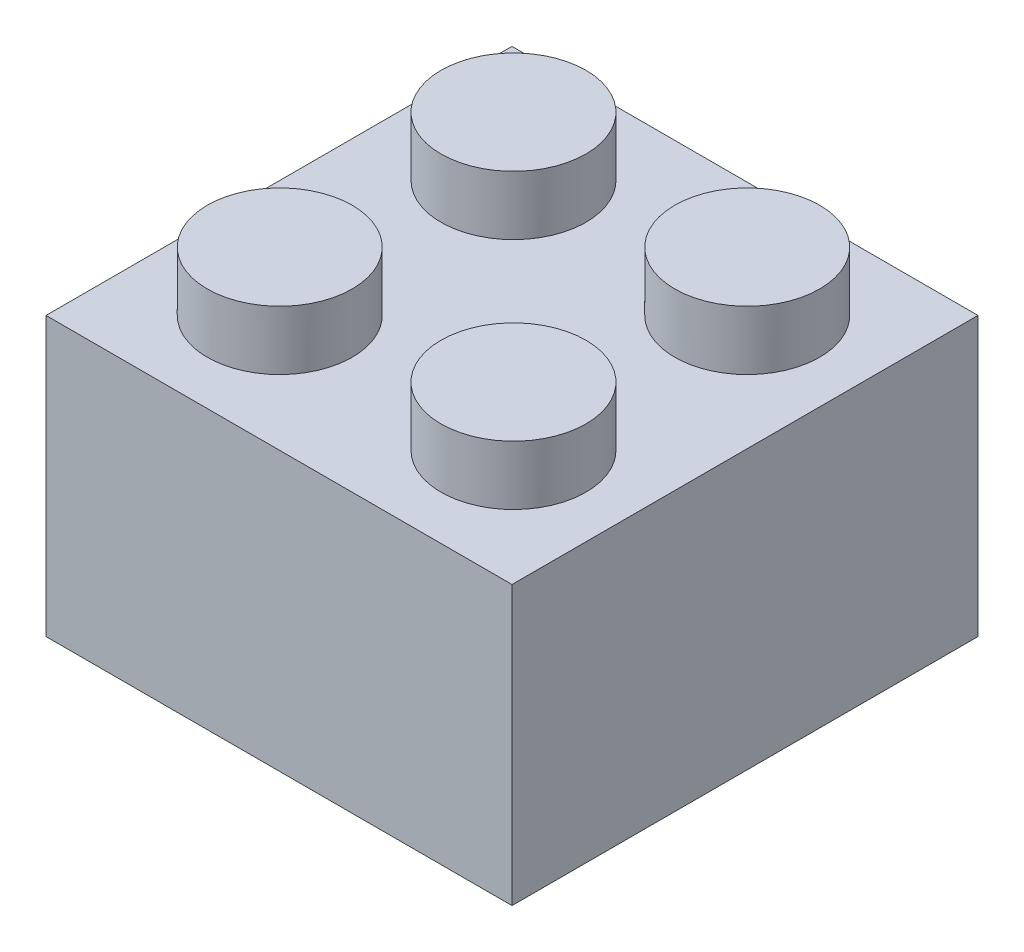
SolidWorks part; units mm, degrees
ref_plane "Front Plane" through (0, 0, 0) normal (0, 0, 1) x (1, 0, 0)
ref_plane "Top Plane" through (0, 0, 0) normal (0, 1, 0) x (1, 0, 0)
ref_plane "Right Plane" through (0, 0, 0) normal (1, 0, 0) x (0, 0, -1)
sketch "stencil" plane through (0, 0, 0) normal (0, 1, 0) x (1, 0, 0)
  line L2 (0, 0) -> (0, 3.95) construction
  line L29 (0, 0) -> (3.95, 0) construction
  line L30 (3.95, 0) -> (3.95, 3.95) construction
  line L31 (7.9, 0) -> (7.9, 3.95) construction
  line L32 (11.85, 0) -> (11.85, 3.95) construction
  line L36 (3.95, 3.95) -> (3.95, 7.9) construction
  line L37 (7.9, 3.95) -> (7.9, 7.9) construction
  line L38 (11.85, 3.95) -> (11.85, 7.9) construction
  line L39 (3.95, 7.9) -> (3.95, 11.85) construction
  line L40 (7.9, 7.9) -> (7.9, 11.85) construction
  line L41 (11.85, 7.9) -> (11.85, 11.85) construction
  line L52 (3.95, 11.85) -> (3.95, 15.8) construction
  line L53 (7.9, 11.85) -> (7.9, 15.8) construction
  line L55 (11.85, 11.85) -> (11.85, 15.8) construction
  line L56 (0, 3.95) -> (0, 7.9) construction
  line L57 (0, 7.9) -> (0, 11.85) construction
  line L58 (0, 11.85) -> (0, 15.8) construction
  line L59 (3.95, 0) -> (7.9, 0) construction
  line L60 (7.9, 0) -> (11.85, 0) construction
  line L61 (11.85, 0) -> (15.8, 0) construction
  line L62 (3.95, 3.95) -> (7.9, 3.95) construction
  line L63 (7.9, 3.95) -> (11.85, 3.95) construction
  line L64 (11.85, 3.95) -> (15.8, 3.95) construction
  line L65 (3.95, 7.9) -> (7.9, 7.9) construction
  line L66 (7.9, 7.9) -> (11.85, 7.9) construction
  line L67 (11.85, 7.9) -> (15.8, 7.9) construction
  line L68 (3.95, 11.85) -> (7.9, 11.85) construction
  line L69 (7.9, 11.85) -> (11.85, 11.85) construction
  line L70 (11.85, 11.85) -> (15.8, 11.85) construction
  line L71 (0, 3.95) -> (3.95, 3.95) construction
  line L72 (0, 7.9) -> (3.95, 7.9) construction
  line L73 (0, 11.85) -> (3.95, 11.85) construction
  line L74 (14.35, 14.35) -> (1.45, 14.35)
  line L75 (15.75, 15.75) -> (0.05, 15.75)
  line L76 (15.75, 15.75) -> (15.75, 0.05)
  line L77 (15.75, 0.05) -> (0.05, 0.05)
  line L78 (0.05, 15.75) -> (0.05, 0.05)
  line L79 (7.9, 0.05) -> (7.9, 15.75) construction
  line L80 (15.75, 7.9) -> (0.05, 7.9) construction
  line L81 (1.45, 14.35) -> (1.45, 1.45)
  line L82 (14.35, 1.45) -> (1.45, 1.45)
  line L83 (14.35, 14.35) -> (14.35, 1.45)
  circle A40 centre (7.9, 7.9) radius 3.2
  circle A41 centre (7.9, 7.9) radius 2.4
  circle A42 centre (3.95, 3.95) radius 2.45
  circle A43 centre (11.85, 3.95) radius 2.45
  circle A44 centre (11.85, 11.85) radius 2.45
  circle A45 centre (3.95, 11.85) radius 2.45
  point P6 (3.95, -15.8)
  point P9 (7.9, -15.8)
  point P10 (7.9, -11.85)
  point P13 (3.95, -7.9)
  point P15 (7.9, -7.9)
  point P17 (7.9, -3.95)
  point P18 (3.95, 0)
  point P21 (7.9, 0)
  point P25 (7.9, 3.95)
  point P27 (3.95, 7.9)
  point P28 (7.9, 7.9)
  point P29 (0, -11.85)
  point P30 (0, -7.9)
  point P31 (0, 3.95)
  point P34 (0, -3.95)
  point P36 (0, 15.8)
  point P37 (0, 23.7)
  point P38 (7.9, 23.7)
  point P39 (15.8, 23.7)
  point P40 (15.8, 15.8)
  point P41 (15.8, 7.9)
  dimension "D9" = 6.4
  dimension "D11" = 4.9
  dimension "D1" = 3.95
  dimension "D2" = 3.95
  dimension "D3" = 15.7
  dimension "D8" = 15.7
  dimension "D10" = 0.8
  dimension "D12" = 1.4
  dimension "D4" = 4
  dimension "D5" = 4
  dimension "D6" = 4
  dimension "D7" = 4
sketch "Sketch1" plane through (0, 0, 0) normal (0, 1, 0) x (1, 0, 0)
  line L5 (0, 0) -> (15.75, 0)
  line L6 (0, 0) -> (0, 15.75)
  line L7 (0, 15.75) -> (15.75, 15.75)
  line L8 (15.75, 0) -> (15.75, 15.75)
extrude "Boss-Extrude1" add sketch "Sketch1" along normal mid plane 9.4
sketch "Sketch2" plane through (0, 4.7, 0) normal (0, 1, 0) x (1, 0, 0)
  circle A9 centre (3.95, 3.95) radius 2.45
  circle A10 centre (3.95, 3.95) radius 2.45 construction
  circle A11 centre (11.85, 3.95) radius 2.45
  circle A12 centre (11.85, 11.85) radius 2.45
  circle A13 centre (3.95, 11.85) radius 2.45
extrude "Boss-Extrude2" add sketch "Sketch2" along normal blind 2
sketch "Sketch4" plane through (0, -4.7, 0) normal (0, -1, 0) x (1, 0, 0)
  line L6 (1.45, -1.45) -> (14.35, -1.45)
  line L8 (1.45, -1.45) -> (1.45, -14.35)
  line L9 (1.45, -14.35) -> (14.35, -14.35)
  line L10 (14.35, -1.45) -> (14.35, -14.35)
extrude "Cut-Extrude1" cut sketch "Sketch4" against normal blind 4
sketch "Sketch5" plane through (0, -0.7, 0) normal (0, -1, 0) x (1, 0, 0)
  circle A8 centre (7.9, -7.9) radius 3.2
  circle A9 centre (7.9, -7.9) radius 2.4
  circle A10 centre (7.9, -7.9) radius 3.2 construction
  circle A11 centre (7.9, -7.9) radius 2.4 construction
extrude "Boss-Extrude3" add sketch "Sketch5" along normal up to surface (4 mm away) up to face at (7.9, -4.7, -7.9)
sketch "Sketch7" plane through (0, -0.7, 0) normal (0, -1, 0) x (1, 0, 0)
  line L0 (3.95, -11.85) -> (3.95, -15.8) construction
  line L1 (0, -11.85) -> (3.95, -11.85) construction
  line L2 (0, -3.95) -> (3.95, -3.95) construction
  line L3 (3.95, 0) -> (3.95, -3.95) construction
  line L4 (11.85, 0) -> (11.85, -3.95) construction
  line L5 (11.85, -3.95) -> (15.8, -3.95) construction
  line L6 (11.85, -11.85) -> (15.8, -11.85) construction
  line L7 (11.85, -11.85) -> (11.85, -15.8) construction
  line L8 (14.35, -14.35) -> (1.45, -14.35) construction
  line L9 (1.45, -14.35) -> (1.45, -1.45) construction
  line L10 (14.35, -1.45) -> (1.45, -1.45) construction
  line L11 (14.35, -14.35) -> (14.35, -1.45) construction
  circle A0 centre (3.95, -14.35) radius 0.2
  circle A1 centre (1.45, -11.85) radius 0.2
  circle A2 centre (1.45, -3.95) radius 0.2
  circle A3 centre (3.95, -1.45) radius 0.2
  circle A4 centre (11.85, -1.45) radius 0.2
  circle A5 centre (14.35, -3.95) radius 0.2
  circle A6 centre (14.35, -11.85) radius 0.2
  circle A7 centre (11.85, -14.35) radius 0.2
  dimension "D1" = 0.4
extrude "Boss-Extrude4" [suppressed] add sketch "Sketch7" along normal up to surface (4 mm away) up to face at (7.9, -4.7, -7.9)
equation "\"t\"= 0.10'tolerance"
equation "\"D3@stencil\"=15.8-\"t\""
equation "\"D8@stencil\"=15.8-\"t\""
equation "\"D12@stencil\"=1.50-\"t\""
equation "\"D9@stencil\"=6.5-\"t\""
equation "\"D1@Boss-Extrude1\"=9.5-\"t\""
